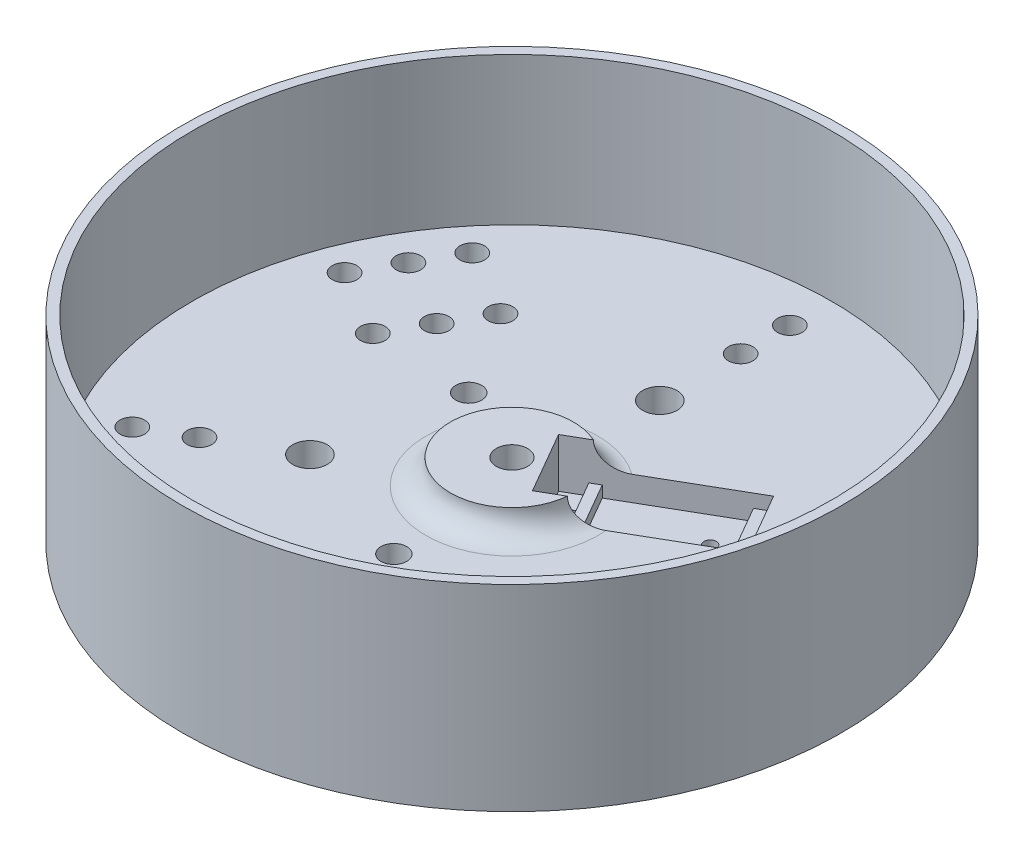
SolidWorks part; units mm, degrees
material "Custom Plastic"
ref_plane "Front Plane" through (0, 0, 0) normal (0, 0, 1) x (1, 0, 0)
ref_plane "Top Plane" through (0, 0, 0) normal (0, 1, 0) x (1, 0, 0)
ref_plane "Right Plane" through (0, 0, 0) normal (1, 0, 0) x (0, 0, -1)
ref_plane "Plane1" through (0, 75, 0) normal (0, 1, 0) x (1, 0, 0)
sketch "Sketch1" plane through (0, 0, 0) normal (0, 1, 0) x (1, 0, 0)
  line L0 (0, 0) -> (0, -65) construction
  line L1 (67.5, 0) -> (-65, 0) construction
  line L2 (-55.608, 32.1053) -> (-46.9587, 47.0864)
  line L3 (0, 0) -> (56.2917, 32.5) construction
  line L4 (0, 0) -> (-56.2917, 32.5) construction
  line L5 (-46.9587, 47.0864) -> (-64.2574, 17.1242)
  line L6 (-53.108, 36.4354) -> (-58.108, 27.7752)
  line L7 (-58.108, 27.7752) -> (-39.4712, 17.0152)
  line L8 (0, -64.2106) -> (-17.2987, -64.2106)
  line L9 (-17.2987, -64.2106) -> (17.2987, -64.2106)
  line L10 (-39.4712, 17.0152) -> (-34.4712, 25.6755)
  line L11 (-58.108, 27.7752) -> (-58.6249, 28.0736)
  line L12 (-53.108, 36.4354) -> (-34.4712, 25.6755)
  line L13 (-50.608, 40.7656) -> (-51.9358, 41.5322)
  line L14 (-60.608, 23.4451) -> (-61.9358, 24.2117)
  line L15 (-50.608, 40.7656) -> (-27.6411, 27.5056) construction
  line L16 (-37.6411, 10.1851) -> (-27.6411, 27.5056) construction
  line L17 (-60.608, 23.4451) -> (-37.6411, 10.1851) construction
  line L18 (55.608, 32.1053) -> (64.2574, 17.1242)
  line L19 (64.2574, 17.1242) -> (46.9587, 47.0864)
  line L20 (58.108, 27.7752) -> (53.108, 36.4354)
  line L21 (53.108, 36.4354) -> (34.4712, 25.6755)
  line L22 (34.4712, 25.6755) -> (39.4712, 17.0152)
  line L23 (53.108, 36.4354) -> (53.6249, 36.7338)
  line L24 (58.108, 27.7752) -> (39.4712, 17.0152)
  line L25 (60.608, 23.4451) -> (61.9358, 24.2117)
  line L26 (-5, -64.2106) -> (5, -64.2106)
  line L27 (5, -64.2106) -> (5, -42.6907)
  line L28 (5, -42.6907) -> (-5, -42.6907)
  line L29 (5, -64.2106) -> (5, -64.8074)
  line L30 (-5, -64.2106) -> (-5, -42.6907)
  line L32 (50.608, 40.7656) -> (51.9358, 41.5322)
  line L33 (60.608, 23.4451) -> (37.6411, 10.1851) construction
  line L34 (27.6411, 27.5056) -> (37.6411, 10.1851) construction
  line L35 (50.608, 40.7656) -> (27.6411, 27.5056) construction
  line L58 (-10, -64.2106) -> (-10, -37.6907) construction
  line L59 (10, -37.6907) -> (-10, -37.6907) construction
  line L60 (10, -64.2106) -> (10, -37.6907) construction
  line L61 (-10, -64.2106) -> (-10, -65.7438)
  line L62 (10, -64.2106) -> (10, -65.7438)
  line L63 (10, -64.2106) -> (10, -64.8074) construction
  circle A0 centre (0, 0) radius 65
  circle A1 centre (0, 0) radius 66.5
  circle A2 centre (0, 0) radius 67
  circle A4 centre (0, 0) radius 4.125
  circle A5 centre (0, 0) radius 11.1125
  point P14 (1.25, 0)
  point P26 (-36.9712, 21.3454)
  point P39 (0, -42.6907)
  point P51 (36.9712, 21.3454)
  point P58 (0, 0)
  point P67 (0, 0)
  point P68 (0, 0)
  point P71 (0, 0)
  point P81 (0, 0)
  dimension "D1" = 130
  dimension "D2" = 133
  dimension "D3" = 35
  dimension "D5" = 30
  dimension "D11" = 8.25
  dimension "D12" = 22.225
  dimension "D8" = 3
  dimension "D9" = 2
  dimension "D10" = 22.3093
  dimension "D4" = 30
  dimension "D7" = 5
  dimension "D6" = 5
extrude "Boss-Extrude7" add sketch "Sketch1" along normal blind 10 separate body contours L5 A1 L9 A0 | L14 A1 L5 A0 | L13 A1 L14 A0 | L5 A1 L13 A0 | L19 A1 L5 A0 | L32 A1 L19 A0 | L25 A1 L32 A0 | L19 A1 L25 A0 | L9 A1 L19 A0 | L9 A1 L61 A0 | L61 A1 L62 A0 | L62 A1 L9 A0 region at (-56.7202, 0, -32.7474) region at (-49.8038, 0, -43.2312) region at (-48.6682, 0, -43.9168) region at (-57.1937, 0, 33.0208) region at (-62.3413, 0, -21.5157) region at (49.8038, 0, -43.2312) region at (-12.5375, 0, 64.747) region at (56.7202, 0, -32.7474) region at (0, 0, 65.4948) region at (62.3413, 0, -21.5157) region at (12.5375, 0, 64.747) region at (64.9042, 0, -8.5)
extrude "Boss-Extrude8" add sketch "Sketch1<23>" along normal blind 10 contours L9 A0 L18 L19 L24 L22 L21 L2 L5 L12 L10 L7 L8 L30 L28 L27 | L11 A0 L14 L5 | L13 A0 L11 L5 L2 | A0 | A4 region at (-55.2563, 0, -33.3861) region at (-50.2707, 0, -37.6841) region at (-59.1838, 0, -26.3345)
sketch "Sketch1<23>" plane through (0, 0, 0) normal (0, 1, 0) x (1, 0, 0) same geometry as "Sketch1"
sketch "Sketch16" plane through (0, 75, 0) normal (0, -1, 0) x (1, 0, 0)
  line L0 (-31.4672, -29.1372) -> (-40.9672, -12.6828)
  line L1 (-45.0465, -36.9772) -> (-54.5465, -20.5228)
  line L2 (-9.5, 57.5) -> (9.5, 57.5)
  line L3 (-9.5, 41.82) -> (9.5, 41.82)
  line L4 (0, 65) -> (0, 0) construction
  line L5 (-65, 0) -> (67.5, 0) construction
  line L11 (54.5465, -20.5228) -> (45.0465, -36.9772)
  line L13 (40.9672, -12.6828) -> (31.4672, -29.1372)
  line L14 (0, 0) -> (56.2917, -32.5) construction
  line L15 (0, 0) -> (-56.2917, -32.5) construction
  circle A2 centre (0, 0) radius 68.75
  circle A3 centre (0, 0) radius 67.5
  circle A4 centre (36.2172, -20.91) radius 2.5
  circle A5 centre (49.7965, -28.75) radius 2.5
  circle A6 centre (-40.9672, -12.6828) radius 2.5
  circle A7 centre (-36.2172, -20.91) radius 2.5
  circle A8 centre (-49.7965, -28.75) radius 2.5
  circle A9 centre (0, 41.82) radius 2.5
  circle A10 centre (0, 57.5) radius 2.5
  circle A11 centre (-31.4672, -29.1372) radius 2.5
  circle A12 centre (-45.0465, -36.9772) radius 2.5
  circle A13 centre (-54.5465, -20.5228) radius 2.5
  circle A14 centre (9.5, 41.82) radius 2.5
  circle A15 centre (-9.5, 41.82) radius 2.5
  circle A16 centre (-9.5, 57.5) radius 2.5
  circle A17 centre (9.5, 57.5) radius 2.5
  circle A18 centre (31.4672, -29.1372) radius 2.5
  circle A19 centre (40.9672, -12.6828) radius 2.5
  circle A20 centre (54.5465, -20.5228) radius 2.5
  circle A21 centre (45.0465, -36.9772) radius 2.5
  point P23 (0, 0)
  point P24 (-36.2172, -20.91)
  point P27 (-49.7965, -28.75)
  point P31 (0, 41.82)
  dimension "D4" = 15.68
  dimension "D5" = 7.5
  dimension "D1" = 137.5
  dimension "D2" = 135
  dimension "D3" = 5
  dimension "D8" = 5
  dimension "D7" = 19
  dimension "D6" = 3
  dimension "D9" = 3
extrude "Cut-Extrude1" cut sketch "Sketch16" along normal blind 20 from surface contours A10 | A9 | A7 | A8 | A6 | A13 | A12 | A11 | A15 | A16 | A17 | A14 starting at face at (0, 10, 66.5)
sketch "Sketch17" plane through (0, 10, 0) normal (0, 1, 0) x (1, 0, 0)
  circle A0 centre (0, 0) radius 12.5
  circle A1 centre (0, 0) radius 3.175
  dimension "D1" = 25
  dimension "D2" = 6.35
extrude "Boss-Extrude9" add sketch "Sketch17" along normal blind 5.5 from offset 0.5 offset against normal yes
fillet "Fillet1" radius 5 1 edges at (0, 10, 12.5)
sketch "Sketch18" plane through (0, 10, 0) normal (0, 1, 0) x (1, 0, 0)
  line L0 (0, 0) -> (0, 66.5) construction
  line L1 (0, 0) -> (57.5907, -33.25)
  line L2 (0, 0) -> (-57.5907, -33.25)
  line L3 (0, 66.5) -> (0, 56.5) construction
  line L4 (0, 56.5) -> (0, 46.5) construction
  circle A0 centre (0, 0) radius 66.5
  circle A1 centre (0, 56.5) radius 2.5
  circle A2 centre (0, 46.5) radius 2.5
  circle A3 centre (48.9304, -28.25) radius 2.5
  circle A4 centre (40.2702, -23.25) radius 2.5
  circle A5 centre (-48.9304, -28.25) radius 2.5
  circle A6 centre (-40.2702, -23.25) radius 2.5
  circle A7 centre (26.0352, -15.0314) radius 3.5
  circle A8 centre (-26.0352, -15.0314) radius 3.5
  circle A9 centre (0, 30.0628) radius 3.5
  point P21 (0, 0)
  point P28 (0, 0)
  dimension "D1" = 133
  dimension "D6" = 5
  dimension "D8" = 7
  dimension "D2" = 120
  dimension "D3" = 120
  dimension "D4" = 10
  dimension "D5" = 10
  dimension "D7" = 3
  dimension "D9" = 3
extrude "Cut-Extrude2" cut sketch "Sketch18" against normal blind 10 contours A1 | A2 | A4 | A3 | A6 | A5 | A7 | A8 | A9 region at (0, 10, -56.5) region at (0, 10, -46.5)
sketch "Sketch20" plane through (0, 10, 0) normal (0, 1, 0) x (1, 0, 0)
  line L0 (0, 0) -> (-36.2172, 20.91)
  line L1 (0, 0) -> (36.2172, 20.91)
  line L2 (0, 0) -> (0, -41.82)
  line L3 (-6.5, -28.0056) -> (-12, -14.407)
  line L4 (6.5, -28.0056) -> (12, -14.407)
  line L5 (-21.0035, 19.632) -> (-6.4769, 17.5958)
  line L6 (-27.5035, 8.3736) -> (-18.4769, -3.1888)
  line L7 (27.5035, 8.3736) -> (18.4769, -3.1888)
  line L8 (21.0035, 19.632) -> (6.4769, 17.5958)
  circle A0 centre (0, 0) radius 24
  circle A1 centre (-20.7846, 12) radius 2
  circle A2 centre (20.7846, 12) radius 2
  circle A3 centre (0, -24) radius 2
  circle A4 centre (0, 0) radius 18.75
  circle A5 centre (0, 0) radius 28.75
  circle A6 centre (0, 0) radius 7.5
  circle A7 centre (0, 0) radius 12.5
  circle A8 centre (0, 0) radius 10
  circle A9 centre (0, 0) radius 5.25
  circle A10 centre (-20.7846, 12) radius 2.625
  circle A11 centre (0, -24) radius 2.625
  circle A12 centre (20.7846, 12) radius 2.625
  point P32 (0, 0)
  dimension "D1" = 4
  dimension "D2" = 37.5
  dimension "D3" = 57.5
  dimension "D4" = 48
  dimension "D8" = 10.5
  dimension "D9" = 20
  dimension "D10" = 25
  dimension "D11" = 15
  dimension "D12" = 5.25
  dimension "D5" = 6.5
  dimension "D6" = 12
  dimension "D7" = 3
extrude "Cut-Extrude11" cut sketch "Sketch20" against normal blind 25 contours A10 | A11
extrude "Boss-Extrude10" add sketch "Sketch1<24>" along normal blind 40 contours A2 A1 | L5 A1 L9 A0 | L14 A1 L5 A0 | L13 A1 L14 A0 | L5 A1 L13 A0 | L19 A1 L5 A0 | L32 A1 L19 A0 | L25 A1 L32 A0 | L19 A1 L25 A0 | L9 A1 L19 A0 | L62 A1 L9 A0 | L61 A1 L62 A0 | L9 A1 L61 A0 region at (-56.7202, 0, -32.7474) region at (-49.8038, 0, -43.2312) region at (-48.6682, 0, -43.9168) region at (-57.1937, 0, 33.0208) region at (-62.3413, 0, -21.5157) region at (49.8038, 0, -43.2312) region at (-12.5375, 0, 64.747) region at (56.7202, 0, -32.7474) region at (0, 0, 65.4948) region at (62.3413, 0, -21.5157) region at (12.5375, 0, 64.747) region at (64.9042, 0, -8.5) region at (-66.8105, 0, 0)
sketch "Sketch1<24>" plane through (0, 0, 0) normal (0, 1, 0) x (1, 0, 0) same geometry as "Sketch1"
sketch "Sketch21" plane through (0, 0, 0) normal (0, -1, 0) x (1, 0, 0)
  line L0 (0, 0) -> (74.9096, 0) construction
  line L1 (0, 0) -> (67.1187, -38.751) construction
  line L2 (4.3301, -2.5) -> (6.0622, -3.5) construction
  line L3 (8.5532, -1.1854) -> (5.3032, -6.8146) construction
  line L4 (6.0622, -3.5) -> (7.7942, -4.5) construction
  line L5 (32.0429, -18.5) -> (25.5477, -14.75) construction
  line L6 (28.4179, -24.7787) -> (0.7051, -8.7787)
  line L7 (35.6679, -12.2213) -> (7.9551, 3.7787)
  line L8 (6.1692, -7.3146) -> (4.4372, -6.3146)
  line L9 (9.4192, -1.6854) -> (7.6872, -0.6854)
  line L10 (4.6022, -11.0287) -> (11.8522, 1.5287)
  line L11 (13.5843, 0.5287) -> (6.3343, -12.0287)
  line L12 (7.6872, -0.6854) -> (4.4372, -6.3146)
  line L13 (9.4192, -1.6854) -> (6.1692, -7.3146)
  line L14 (7.9551, 3.7787) -> (0.7051, -8.7787)
  line L15 (35.6679, -12.2213) -> (28.4179, -24.7787)
  line L16 (33.0699, -10.7213) -> (25.8199, -23.2787)
  circle A0 centre (6.9282, -4) radius 1.575
  circle A1 centre (25.5477, -14.75) radius 1.25
  point P7 (32.0429, -18.5)
  point P8 (6.9282, -4)
  dimension "D2" = 3.15
  dimension "D1" = 30
  dimension "D3" = 8
extrude "Cut-Extrude12" cut sketch "Sketch21" against normal blind 50 from offset 0.2 contours A0 L13 L9 L12 | L13 A0 L12 | A0 L12 L8 L13 region at (6.9282, 0, -4) region at (5.7518, 0, -6.0375) region at (8.1046, 0, -1.9625) offset against normal yes
extrude "Cut-Extrude13" cut sketch "Sketch21<3>" against normal blind 15 from offset 5 contours A0 L13 L8 L12 L9 L10 L7 L14 L6 | L16 L7 L11 L6 A1 | L12 A0 | L13 A0 L10 region at (19.6128, 0, -11.3234) region at (2.7464, 0, -9.7432) region at (7.9835, 0, -4.6093) region at (5.8595, 0, -3.383) offset against normal yes
sketch "Sketch21<3>" plane through (0, 0, 0) normal (0, -1, 0) x (1, 0, 0) same geometry as "Sketch21"
extrude "Cut-Extrude14" cut sketch "Sketch21<4>" against normal blind 15 from offset 7.3 contours A0 L10 L6 L11 L7 | L7 L16 L6 L15 | L10 A0 region at (30.7439, 0, -17.75) region at (9.0947, 0, -5.2508) region at (8.2533, 0, -4.765) offset against normal yes
sketch "Sketch21<4>" plane through (0, 0, 0) normal (0, -1, 0) x (1, 0, 0) same geometry as "Sketch21"
extrude "Cut-Extrude15" cut sketch "Sketch21<5>" against normal blind 15 contours A1
sketch "Sketch21<5>" plane through (0, 0, 0) normal (0, -1, 0) x (1, 0, 0) same geometry as "Sketch21"
